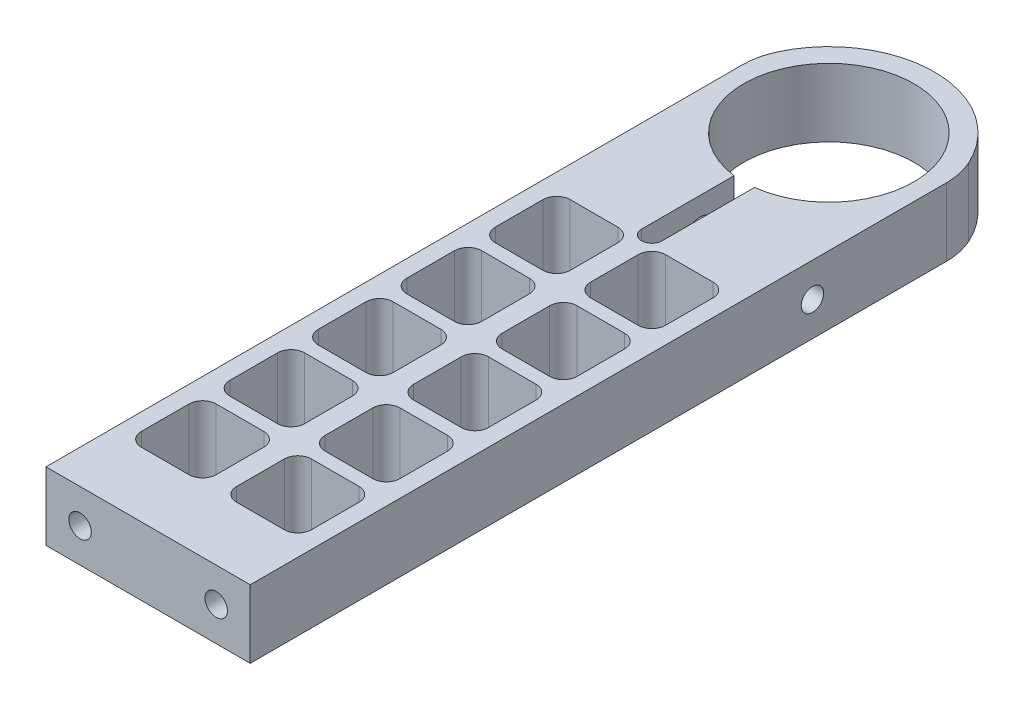
SolidWorks part; units mm, degrees
material "3.1355 (EN-AW 2024)"
ref_plane "Спереди" through (0, 0, 0) normal (0, 0, 1) x (1, 0, 0)
ref_plane "Сверху" through (0, 0, 0) normal (0, 1, 0) x (1, 0, 0)
ref_plane "Справа" through (0, 0, 0) normal (1, 0, 0) x (0, 0, -1)
sketch "Эскиз1" plane through (0, 0, 0) normal (0, 1, 0) x (1, 0, 0)
  line L0 (0, 0) -> (0, -100) construction
  line L1 (-15.5, 0) -> (-15.5, -100)
  line L2 (-15.5, -100) -> (15.5, -100)
  line L3 (15.5, -100) -> (15.5, 0)
  circle A0 centre (0, 0) radius 12.5
  arc A1 (15.5, 0) -> (-15.5, 0) centre (0, 0) ccw
  dimension "D1" = 25
  dimension "D2" = 31
  dimension "D3" = 100
extrude "Бобышка-Вытянуть1" add sketch "Эскиз1" along normal blind 10
sketch "Эскиз6" plane through (0, 10, 0) normal (0, 1, 0) x (1, 0, 0)
  line L0 (0, -12.5) -> (0, -27.5) construction
  line L1 (-15.5, -100) -> (15.5, -100) construction
  line L2 (0, -100) -> (0, -90) construction
  line L3 (-1.5, -12.4097) -> (-1.5, -26)
  line L4 (1.5, -12.4097) -> (1.5, -26)
  line L5 (-1.5, -12.5) -> (-1.5, -27.5) construction
  line L6 (1.5, -12.5) -> (1.5, -27.5) construction
  line L7 (-1.5, -27.5) -> (1.5, -27.5) construction
  line L9 (-1.5, -42.5) -> (-1.5, -49.5)
  line L10 (-10.5, -51.5) -> (-3.5, -51.5)
  line L11 (-12.5, -42.5) -> (-12.5, -49.5)
  line L12 (-10.5, -40.5) -> (-3.5, -40.5)
  line L13 (-1.5, -55.5) -> (-1.5, -62.5)
  line L14 (-10.5, -64.5) -> (-3.5, -64.5)
  line L15 (-12.5, -55.5) -> (-12.5, -62.5)
  line L16 (-10.5, -53.5) -> (-3.5, -53.5)
  line L17 (-1.5, -68.5) -> (-1.5, -75.5)
  line L18 (-10.5, -77.5) -> (-3.5, -77.5)
  line L19 (-12.5, -68.5) -> (-12.5, -75.5)
  line L20 (-10.5, -66.5) -> (-3.5, -66.5)
  line L21 (-1.5, -81.5) -> (-1.5, -88.5)
  line L22 (-10.5, -90.5) -> (-3.5, -90.5)
  line L23 (-12.5, -81.5) -> (-12.5, -88.5)
  line L24 (-10.5, -79.5) -> (-3.5, -79.5)
  line L25 (-1.5, -29.5) -> (-1.5, -42.5) construction
  line L26 (12.5, -38.5) -> (1.5, -27.5) construction
  line L27 (12.5, -27.5) -> (1.5, -38.5) construction
  line L28 (1.5, -29.5) -> (1.5, -42.5) construction
  line L29 (1.5, -29.5) -> (1.5, -36.5)
  line L30 (10.5, -38.5) -> (3.5, -38.5)
  line L31 (-12.5, 0) -> (-12.5, -100)
  line L32 (-12.5, -29.5) -> (-12.5, -36.5)
  line L33 (10.5, -27.5) -> (3.5, -27.5)
  line L36 (-10.5, -27.5) -> (-3.5, -27.5)
  line L37 (12.5, -29.5) -> (12.5, -36.5)
  line L38 (-10.5, -38.5) -> (-3.5, -38.5)
  line L39 (-1.5, -29.5) -> (-1.5, -36.5)
  line L40 (-12.5, -27.5) -> (-1.5, -38.5) construction
  line L41 (-12.5, -38.5) -> (-1.5, -27.5) construction
  line L42 (10.5, -79.5) -> (3.5, -79.5)
  line L43 (12.5, -81.5) -> (12.5, -88.5)
  line L44 (10.5, -90.5) -> (3.5, -90.5)
  line L45 (1.5, -81.5) -> (1.5, -88.5)
  line L46 (10.5, -66.5) -> (3.5, -66.5)
  line L47 (12.5, -68.5) -> (12.5, -75.5)
  line L48 (10.5, -77.5) -> (3.5, -77.5)
  line L49 (1.5, -68.5) -> (1.5, -75.5)
  line L50 (10.5, -53.5) -> (3.5, -53.5)
  line L51 (12.5, -55.5) -> (12.5, -62.5)
  line L52 (10.5, -64.5) -> (3.5, -64.5)
  line L53 (1.5, -55.5) -> (1.5, -62.5)
  line L54 (10.5, -40.5) -> (3.5, -40.5)
  line L55 (12.5, -42.5) -> (12.5, -49.5)
  line L56 (10.5, -51.5) -> (3.5, -51.5)
  line L57 (1.5, -42.5) -> (1.5, -49.5)
  circle A0 centre (0, 0) radius 12.5 construction
  arc A1 (-1.5, -12.4097) -> (1.5, -12.4097) centre (0, 0) ccw
  arc A2 (-12.5, -29.5) -> (-10.5, -27.5) centre (-10.5, -29.5) cw
  arc A3 (-12.5, -36.5) -> (-10.5, -38.5) centre (-10.5, -36.5) ccw
  arc A4 (-3.5, -38.5) -> (-1.5, -36.5) centre (-3.5, -36.5) ccw
  arc A5 (-1.5, -29.5) -> (-3.5, -27.5) centre (-3.5, -29.5) ccw
  arc A6 (-1.5, -26) -> (1.5, -26) centre (0, -26) ccw
  arc A7 (-1.5, -42.5) -> (-3.5, -40.5) centre (-3.5, -42.5) ccw
  arc A8 (-3.5, -51.5) -> (-1.5, -49.5) centre (-3.5, -49.5) ccw
  arc A9 (-12.5, -49.5) -> (-10.5, -51.5) centre (-10.5, -49.5) ccw
  arc A10 (-12.5, -42.5) -> (-10.5, -40.5) centre (-10.5, -42.5) cw
  arc A11 (-1.5, -55.5) -> (-3.5, -53.5) centre (-3.5, -55.5) ccw
  arc A12 (-3.5, -64.5) -> (-1.5, -62.5) centre (-3.5, -62.5) ccw
  arc A13 (-12.5, -62.5) -> (-10.5, -64.5) centre (-10.5, -62.5) ccw
  arc A14 (-12.5, -55.5) -> (-10.5, -53.5) centre (-10.5, -55.5) cw
  arc A15 (-1.5, -68.5) -> (-3.5, -66.5) centre (-3.5, -68.5) ccw
  arc A16 (-3.5, -77.5) -> (-1.5, -75.5) centre (-3.5, -75.5) ccw
  arc A17 (-12.5, -75.5) -> (-10.5, -77.5) centre (-10.5, -75.5) ccw
  arc A18 (-12.5, -68.5) -> (-10.5, -66.5) centre (-10.5, -68.5) cw
  arc A19 (-1.5, -81.5) -> (-3.5, -79.5) centre (-3.5, -81.5) ccw
  arc A20 (-3.5, -90.5) -> (-1.5, -88.5) centre (-3.5, -88.5) ccw
  arc A21 (-12.5, -88.5) -> (-10.5, -90.5) centre (-10.5, -88.5) ccw
  arc A22 (-12.5, -81.5) -> (-10.5, -79.5) centre (-10.5, -81.5) cw
  arc A23 (12.5, -81.5) -> (10.5, -79.5) centre (10.5, -81.5) ccw
  arc A24 (12.5, -88.5) -> (10.5, -90.5) centre (10.5, -88.5) cw
  arc A25 (3.5, -90.5) -> (1.5, -88.5) centre (3.5, -88.5) cw
  arc A26 (1.5, -81.5) -> (3.5, -79.5) centre (3.5, -81.5) cw
  arc A27 (12.5, -68.5) -> (10.5, -66.5) centre (10.5, -68.5) ccw
  arc A28 (12.5, -75.5) -> (10.5, -77.5) centre (10.5, -75.5) cw
  arc A29 (3.5, -77.5) -> (1.5, -75.5) centre (3.5, -75.5) cw
  arc A30 (1.5, -68.5) -> (3.5, -66.5) centre (3.5, -68.5) cw
  arc A31 (12.5, -55.5) -> (10.5, -53.5) centre (10.5, -55.5) ccw
  arc A32 (12.5, -62.5) -> (10.5, -64.5) centre (10.5, -62.5) cw
  arc A33 (3.5, -64.5) -> (1.5, -62.5) centre (3.5, -62.5) cw
  arc A34 (1.5, -55.5) -> (3.5, -53.5) centre (3.5, -55.5) cw
  arc A35 (12.5, -42.5) -> (10.5, -40.5) centre (10.5, -42.5) ccw
  arc A36 (12.5, -49.5) -> (10.5, -51.5) centre (10.5, -49.5) cw
  arc A37 (3.5, -51.5) -> (1.5, -49.5) centre (3.5, -49.5) cw
  arc A38 (1.5, -42.5) -> (3.5, -40.5) centre (3.5, -42.5) cw
  arc A39 (1.5, -29.5) -> (3.5, -27.5) centre (3.5, -29.5) cw
  arc A40 (3.5, -38.5) -> (1.5, -36.5) centre (3.5, -36.5) cw
  arc A41 (12.5, -36.5) -> (10.5, -38.5) centre (10.5, -36.5) cw
  arc A42 (12.5, -29.5) -> (10.5, -27.5) centre (10.5, -29.5) ccw
  point P13 (-7, -33)
  point P152 (7, -33)
  dimension "D7" = 2
  dimension "D8" = 5
  dimension "D1" = 15
  dimension "D2" = 10
  dimension "D5" = 3
  dimension "D9" = 13
  dimension "D3" = 1.5
  dimension "D4" = 1.5
extrude "Вырез-Вытянуть5" cut sketch "Эскиз6" against normal through all
sketch "Эскиз7" plane through (15.5, 0, 0) normal (1, 0, 0) x (0, 0, -1)
  line L0 (-12.4097, 5) -> (-17.4097, 5) construction
  line L1 (-12.4097, 0) -> (-12.4097, 10) construction
  dimension "D1" = 5
hole_wizard "Отверстие обработанное метчиком M4x0.71" positions "Эскиз9" profile "Эскиз8" tap size "M4x0.7" standard "Ansi Metric" end condition through all
sketch "Эскиз9" plane through (1.5, 0, 0) normal (-1, 0, 0) x (0, 0, 1)
  point P0 (17.4097, 5)
sketch "Эскиз8" plane through (1.5, 5, 17.4097) normal (0, 1, 0) x (0, 0, 1)
  line L0 (0, 0) -> (0, 14)
  line L1 (0, 14) -> (1.65, 14)
  line L2 (1.65, 14) -> (1.65, 0)
  line L5 (1.65, 0) -> (0, 0)
  line L11 (0, -6.35) -> (0, 107.95) construction
  dimension "Диаметр проходного сверла" = 3.3
  dimension "Глубина проходного сверла" = 14
cosmetic thread "Отверстие резьбы1" parameters "D2"=4
hole_wizard "Цековка для винта с внутренним шестигранником M41" positions "Эскиз11" profile "Эскиз10" counterbore size "M4" standard "Ansi Metric" end condition up to next
sketch "Эскиз11" plane through (-15.5, 0, 0) normal (-1, 0, 0) x (0, 0, 1)
  point P0 (17.4097, 5)
sketch "Эскиз10" plane through (-15.5, 5, 17.4097) normal (0, 1, 0) x (0, 0, 1)
  line L0 (0, 0) -> (0, 14)
  line L1 (0, 14) -> (2.25, 14)
  line L3 (2.25, 14) -> (2.25, 4.5)
  line L4 (2.25, 4.5) -> (4, 4.5)
  line L5 (4, 4.5) -> (4, 0)
  line L7 (4, 0) -> (0, 0)
  line L11 (0, -6.35) -> (0, 107.95) construction
  dimension "Диаметр сквозного отверстия" = 4.5
  dimension "Глубина сквозного отверстия" = 14
  dimension "Диаметр цековки" = 8
  dimension "Глубина цековки" = 4.5
sketch "Эскиз12" plane through (0, 10, 0) normal (0, 1, 0) x (1, 0, 0)
  line L2 (-15, 0) -> (-15, -100)
  line L3 (-15, 3.9051) -> (-15, -100)
  line L4 (-15, -100) -> (-15.5, -100)
  line L5 (15, -100) -> (15, 0)
  line L6 (15, -100) -> (15, 3.9051)
  line L7 (-15.5, -100) -> (-15.5, 0)
  line L8 (15, -100) -> (15.5, -100)
  line L9 (15.5, -100) -> (15.5, 0)
  arc A0 (15.5, 0) -> (-15.5, 0) centre (0, 0) ccw construction
  arc A1 (15.5, 0) -> (15, 3.9051) centre (0, 0) ccw
  arc A2 (-15, 3.9051) -> (-15.5, 0) centre (0, 0) ccw
  dimension "D1" = 0.5
  dimension "D2" = 0.5
extrude "Вырез-Вытянуть6" cut sketch "Эскиз12" against normal blind 10
fillet "Скругление1" radius 10 2 edges at (-15, 5, -3.9051) (15, 5, -3.9051)
hole_wizard "Отверстие обработанное метчиком M4x0.72" positions "Эскиз14" profile "Эскиз13" tap size "M4x0.7" standard "Ansi Metric"
sketch "Эскиз14" plane through (0, 0, 100) normal (0, 0, 1) x (1, 0, 0)
  point P0 (-9.9983, 5)
  point P3 (10.0017, 5)
cosmetic thread "Отверстие резьбы2" parameters "D1"=9.8649, "D2"=4
cosmetic thread "Отверстие резьбы3" parameters "D1"=9.8625, "D2"=4
sketch "Эскиз13" plane through (-9.9983, 5, 100) normal (1, 0, 0) x (0, -1, 0)
  line L0 (0, 0) -> (0, 10.9914)
  line L1 (0, 10.9914) -> (1.65, 10)
  line L2 (1.65, 10) -> (1.65, 0)
  line L5 (1.65, 0) -> (0, 0)
  line L10 (0, 10.9914) -> (-1.65, 10) construction
  line L11 (0, -6.35) -> (0, 107.95) construction
  dimension "Диаметр сверла" = 3.3
  dimension "Глубина сверла" = 10
  dimension "Угол заточки сверла" = 118
equation "\"D2@Эскиз1\"=\"D1@Эскиз1\"+6"
